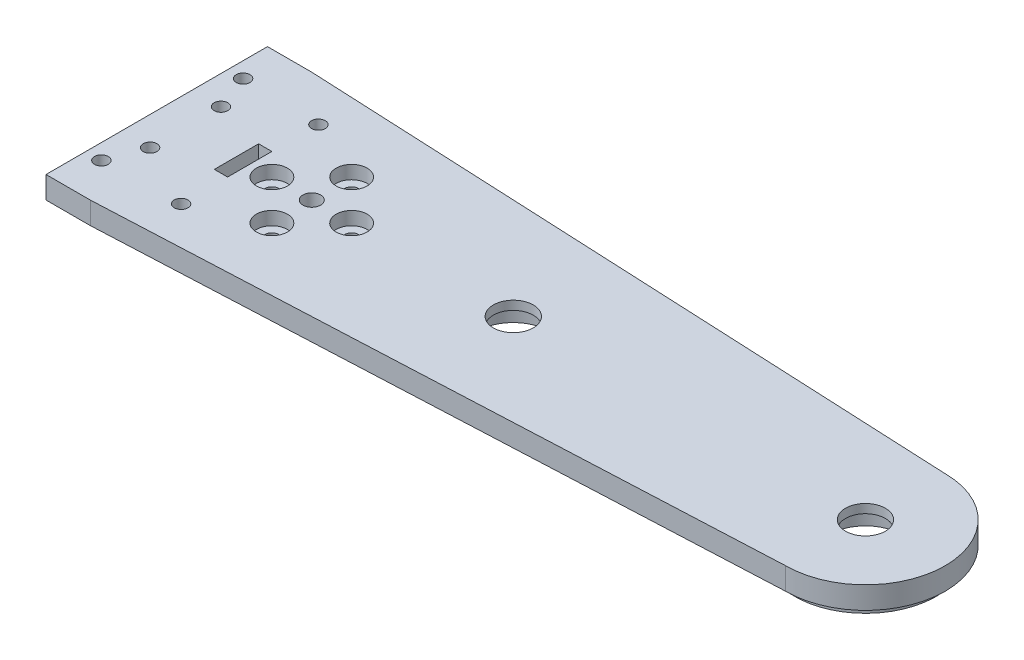
SolidWorks part; units mm, degrees
ref_plane "Front Plane" through (0, 0, 0) normal (0, 0, 1) x (1, 0, 0)
ref_plane "Top Plane" through (0, 0, 0) normal (0, 1, 0) x (1, 0, 0)
ref_plane "Right Plane" through (0, 0, 0) normal (1, 0, 0) x (0, 0, -1)
sketch "Sketch28" plane through (-32, 0, 0) normal (0, -1, 0) x (0, 0, 1)
  line L1 (0, -20) -> (0, -65.5) construction
  line L2 (-8, 8.5) -> (8, 8.5) construction
  line L3 (0, 15) -> (0, -3) construction
  line L8 (-25, 15) -> (25, 15)
  line L12 (25, 15) -> (25, 5)
  line L13 (-25, 15) -> (-25, 5)
  line L14 (-25, 5) -> (-18, -145)
  line L15 (18, -145) -> (25, 5)
  line L16 (-25, 5) -> (-25, 8.5) construction
  line L17 (-25, 8.5) -> (-8, 8.5) construction
  line L18 (-25, 15) -> (-25, 11.5) construction
  line L19 (-25, 11.5) -> (-16, 11.5) construction
  line L20 (-16, 11.5) -> (16, 11.5) construction
  line L21 (-5, -3) -> (5, -3)
  line L26 (5, -3) -> (5, -6)
  line L27 (5, -6) -> (-5, -6)
  line L28 (-5, -6) -> (-5, -3)
  line L29 (-5, -3) -> (-15.5, -3) construction
  line L30 (-15.5, -3) -> (-15.5, -6) construction
  line L31 (5, -3) -> (15.5, -3) construction
  line L32 (15.5, -3) -> (15.5, -6) construction
  line L33 (0, -20) -> (0, -6) construction
  line L34 (0, -65.5) -> (0, -145) construction
  circle A7 centre (8, 8.5) radius 1.55
  circle A8 centre (-8, 8.5) radius 1.55
  circle A9 centre (16, 11.5) radius 1.55
  circle A10 centre (-16, 11.5) radius 1.55
  circle A13 centre (-15.5, -6) radius 1.55
  circle A14 centre (15.5, -6) radius 1.55
  circle A15 centre (0, -20) radius 12.5 construction
  circle A19 centre (0, -65.5) radius 4.5
  circle A20 centre (0, -20) radius 2
  circle A21 centre (0, -145) radius 4.5
  arc A22 (-18, -145) -> (18, -145) centre (0, -145) ccw
  circle A23 centre (0, -20) radius 9 construction
  circle A24 centre (-9, -20) radius 1.55
  circle A25 centre (0, -11) radius 1.55
  circle A26 centre (9, -20) radius 1.55
  circle A27 centre (0, -29) radius 1.55
  point P13 (0, 15)
  point P27 (0, -3)
  point P51 (0, -20)
extrude "Boss-Extrude10" add sketch "Sketch28" along normal blind 5
sketch "Sketch29" plane through (0, -5, 0) normal (0, -1, 0) x (1, 0, 0)
  circle A0 centre (33.5, 0) radius 16
  circle A5 centre (113, 0) radius 16
extrude "Boss-Extrude11" add sketch "Sketch29" along normal blind 2
sketch "Sketch30" plane through (0, -7, 0) normal (0, -1, 0) x (1, 0, 0)
  circle A0 centre (33.5, 0) radius 8.2
  circle A1 centre (113, 0) radius 8.2
extrude "Cut-Extrude1" cut sketch "Sketch30" against normal blind 5
sketch "Sketch31" plane through (0, 0, 0) normal (0, 1, 0) x (1, 0, 0)
  circle A0 centre (-12, 9) radius 3.5
  circle A1 centre (-3, 0) radius 3.5
  circle A2 centre (-12, -9) radius 3.5
  circle A3 centre (-21, 0) radius 3.5
  point P12 (-12, 0)
extrude "Cut-Extrude2" cut sketch "Sketch31" against normal blind 3
